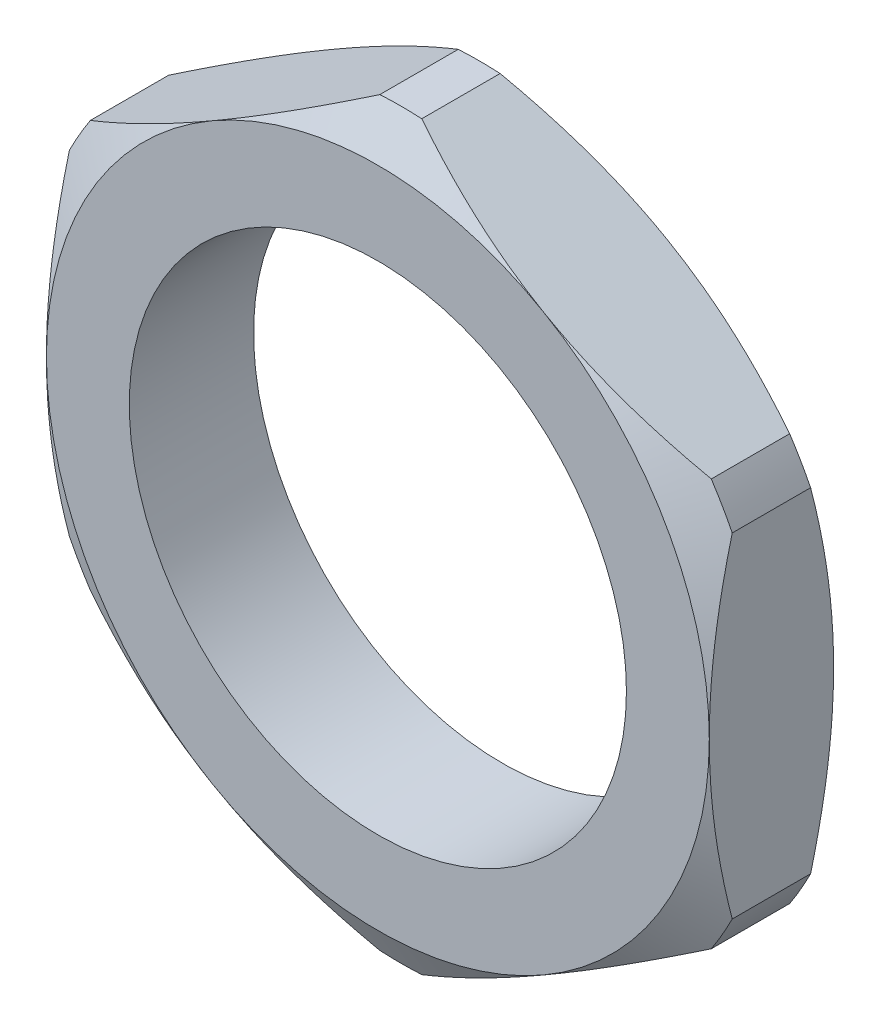
SolidWorks part; units mm, degrees
ref_plane "Front Plane" through (0, 0, 0) normal (0, 0, 1) x (1, 0, 0)
ref_plane "Top Plane" through (0, 0, 0) normal (0, 1, 0) x (1, 0, 0)
ref_plane "Right Plane" through (0, 0, 0) normal (1, 0, 0) x (0, 0, -1)
sketch "Sketch1" plane through (0, 0, 0) normal (1, 0, 0) x (0, 0, -1)
  line L0 (-1.1906, 0) -> (1.1906, 0) construction
  line L5 (0, 6.35) -> (0, -6.35) construction
  point P5 (0, 4.7625)
  point P6 (0, -4.7625)
  point P7 (-0.3969, 0)
  dimension "Height" = 2.3813
  dimension "Width" = 12.7
  dimension "Thread Size Decimal Equivalent" = 9.525
  dimension "Thread Pitch" = 0.7937
sketch "Sketch2" plane through (0, 0, 0) normal (1, 0, 0) x (0, 0, -1)
  line L0 (-1.1906, 6.35) -> (-0.7507, 7.112)
  line L1 (-1.1906, 6.35) -> (1.1906, 6.35)
  line L2 (-1.1906, 6.35) -> (-1.1906, 4.7625)
  line L3 (-1.1906, 4.7625) -> (1.1906, 4.7625)
  line L4 (1.1906, 6.35) -> (1.1906, 4.7625)
  line L5 (-0.7507, 7.112) -> (0.7507, 7.112)
  line L6 (0.7507, 7.112) -> (1.1906, 6.35)
  line L7 (-1.1906, 0) -> (1.1906, 0) construction
  line L8 (-1.1906, 0) -> (1.1906, 0) construction
  line L9 (-1.9348, 4.8484) -> (-1.5379, 4.161) construction
  line L10 (-1.5379, 4.161) -> (-1.141, 4.8484) construction
  line L11 (-1.141, 4.8484) -> (-1.9348, 4.8484) construction
  line L12 (-1.8852, 4.7625) -> (-1.1906, 4.7625) construction
  line L13 (-1.5379, 4.8484) -> (-1.5379, 4.7625) construction
  line L14 (-1.5379, 4.7625) -> (-1.5379, 4.2469) construction
  line L15 (-1.5379, 4.2469) -> (-1.5379, 4.161) construction
  line L16 (-1.5875, 4.2469) -> (-1.4883, 4.2469)
  line L17 (-1.91, 4.8055) -> (-1.1658, 4.8055)
  line L18 (-1.4883, 4.2469) -> (-1.1658, 4.8055)
  line L19 (-1.5875, 4.2469) -> (-1.91, 4.8055)
  point P25 (-1.5379, 4.8055)
  dimension "D1" = 14.224
  dimension "D2" = 60
  dimension "D3" = 0.7937
  dimension "D4" = 0.0992
sketch "Drawing Ref" plane through (0, 0, 0) normal (0, 0, 1) x (1, 0, 0)
  line L0 (0, 0) -> (0, -4.8484) construction
  line L1 (0, 0) -> (3.4284, -3.4284) construction
  circle A0 centre (0, 0) radius 4.8484 construction
  dimension "D1" = 45
sketch "Sketch3" plane through (0, 0, 0) normal (1, 0, 0) x (0, 0, -1)
  line L0 (-1.1906, 6.35) -> (-0.7507, 7.112) construction
  line L1 (-0.7507, 7.112) -> (0.7507, 7.112) construction
  line L2 (0.7507, 7.112) -> (1.1906, 6.35) construction
  line L3 (1.1906, 6.35) -> (1.1906, 4.7625) construction
  line L4 (-1.1906, 4.7625) -> (1.1906, 4.7625) construction
  line L5 (-1.1906, 6.35) -> (-1.1906, 4.7625) construction
  line L6 (-1.1906, 6.35) -> (-0.7507, 7.112)
  line L7 (-0.7507, 7.112) -> (0.7507, 7.112)
  line L8 (0.7507, 7.112) -> (1.1906, 6.35)
  line L9 (1.1906, 6.35) -> (1.1906, 4.7625)
  line L10 (-1.1906, 4.7625) -> (1.1906, 4.7625)
  line L11 (-1.1906, 6.35) -> (-1.1906, 4.7625)
revolve "Revolve1" add sketch "Sketch3" angle 360 about L0
sketch "Sketch4" plane through (0, 0, 0) normal (0, 0, 1) x (1, 0, 0)
  line L1 (0, 7.3323) -> (-6.35, 3.6662)
  line L2 (-6.35, 3.6662) -> (-6.35, -3.6662)
  line L3 (-6.35, -3.6662) -> (0, -7.3323)
  line L4 (0, -7.3323) -> (6.35, -3.6662)
  line L5 (6.35, -3.6662) -> (6.35, 3.6662)
  line L6 (6.35, 3.6662) -> (0, 7.3323)
  circle A0 centre (0, 0) radius 6.35 construction
extrude "Cut-Extrude1" cut sketch "Sketch4" against normal through all both and the other way through all flip side to cut
sketch "Sketch5" [suppressed] plane through (0, 0, 1.1906) normal (0, 0, 1) x (1, 0, 0)
  circle A0 centre (0, 0) radius 4.7625
curve "Helix/Spiral1" [suppressed] pitch 0.7937 height 3.175 turns 4
sketch "Sketch6" [suppressed] plane through (0, 0, 0) normal (1, 0, 0) x (0, 0, -1)
  line L0 (-1.5875, 4.2469) -> (-1.4883, 4.2469) construction
  line L1 (-1.5875, 4.2469) -> (-1.91, 4.8055) construction
  line L2 (-1.91, 4.8055) -> (-1.1658, 4.8055) construction
  line L3 (-1.4883, 4.2469) -> (-1.1658, 4.8055) construction
  line L4 (-1.5875, 4.2469) -> (-1.4883, 4.2469)
  line L5 (-1.5875, 4.2469) -> (-1.91, 4.8055)
  line L6 (-1.91, 4.8055) -> (-1.1658, 4.8055)
  line L7 (-1.4883, 4.2469) -> (-1.1658, 4.8055)
sweep "Sweep1" [suppressed] add profiles "Sketch6" path "Helix/Spiral1"
sketch "Sketch7" [suppressed] plane through (0, 0, 1.1906) normal (0, 0, 1) x (1, 0, 0)
  circle A0 centre (0, 0) radius 4.8484
extrude "Cut-Extrude3" [suppressed] cut sketch "Sketch7" against normal through all draft 45 and the other way through all
mirror "Mirror1" [suppressed] about plane through (0, 0, 0) normal (0, 0, 1)
equation "\"D1@Sketch2\"=\"Width@Sketch1\" * 1.12"
equation "\"D4@Sketch2\"=\"Thread Pitch@Sketch1\"/8"
equation "\"D3@Sketch2\"=\"Thread Pitch@Sketch1\""
equation "\"D4@Helix/Spiral1\"=\"Thread Pitch@Sketch1\""
equation "\"D3@Helix/Spiral1\"=\"Height@Sketch1\"+\"Thread Pitch@Sketch1\""
